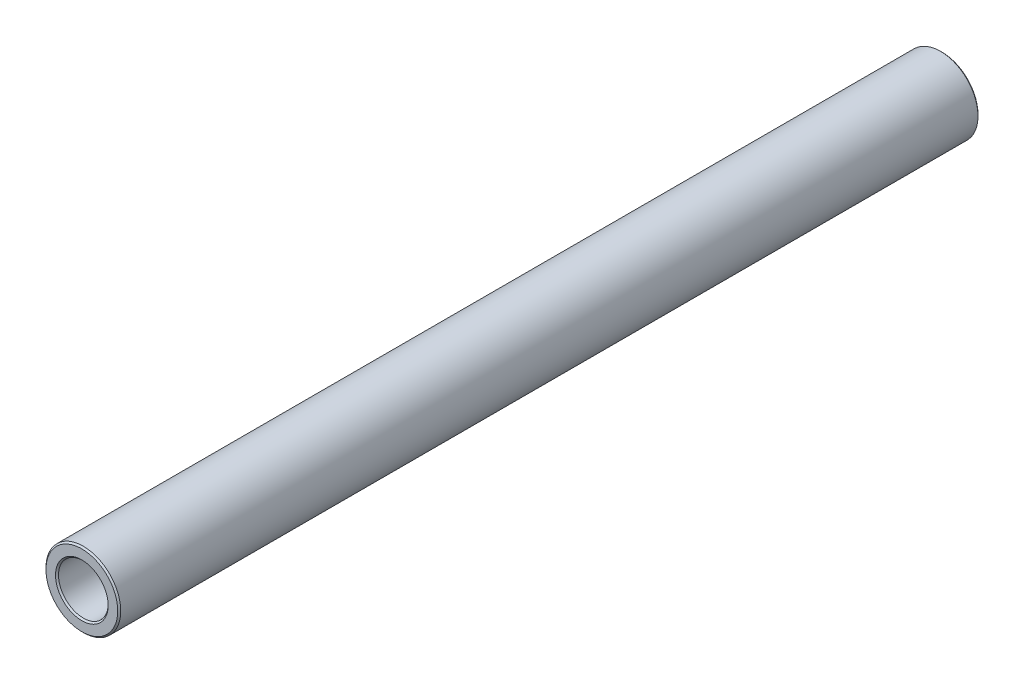
SolidWorks part; units mm, degrees
material "6061 Alloy"
ref_plane "Front Plane" through (0, 0, 0) normal (0, 0, 1) x (1, 0, 0)
ref_plane "Top Plane" through (0, 0, 0) normal (0, 1, 0) x (1, 0, 0)
ref_plane "Right Plane" through (0, 0, 0) normal (1, 0, 0) x (0, 0, -1)
sketch "Sketch1" plane through (0, 0, 0) normal (0, 0, 1) x (1, 0, 0)
  circle A0 centre (0, 0) radius 2.1082
  circle A1 centre (0, 0) radius 3.175
  dimension "D1" = 6.35
  dimension "D2" = 4.2164
extrude "Boss-Extrude1" add sketch "Sketch1" along normal blind 73.025
chamfer "Chamfer1" distance 0.127 angle 45 4 edges at (2.1082, 0, 0) (3.175, 0, 0) (2.1082, 0, 73.025) (3.175, 0, 73.025)
